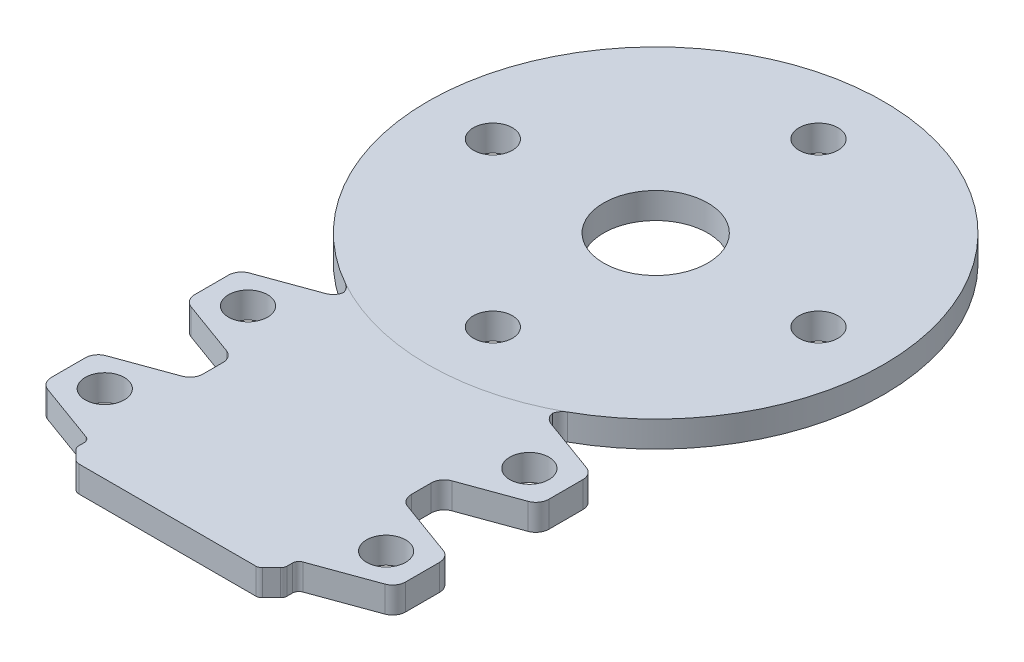
SolidWorks part; units mm, degrees
ref_plane "Front Plane" through (0, 0, 0) normal (0, 0, 1) x (1, 0, 0)
ref_plane "Top Plane" through (0, 0, 0) normal (0, 1, 0) x (1, 0, 0)
ref_plane "Right Plane" through (0, 0, 0) normal (1, 0, 0) x (0, 0, -1)
sketch "Sketch1" plane through (0, 0, 0) normal (0, 1, 0) x (1, 0, 0)
  circle A0 centre (0, 0) radius 4
  circle A1 centre (0, 0) radius 17.5
  circle A2 centre (0, 12.5) radius 1.5
  circle A3 centre (0, 0) radius 17.5
  circle A4 centre (12.5, 0) radius 1.5
  circle A5 centre (0, 0) radius 17.5
  circle A6 centre (0, -12.5) radius 1.5
  circle A7 centre (0, 0) radius 17.5
  circle A8 centre (-12.5, 0) radius 1.5
  point P18 (0, 0)
  dimension "D1" = 17.5
  dimension "D2" = 8
  dimension "D3" = 3
  dimension "D4" = 12.5
  dimension "D5" = 4
sketch "Sketch2" plane through (0, 0, 0) normal (0, 1, 0) x (1, 0, 0)
  line L0 (8, -37.5) -> (-8, -37.5)
  line L1 (-8, -4) -> (8, -4)
  line L2 (-8, -4) -> (-8, -37.5)
  line L3 (8, -4) -> (8, -37.5)
  circle A0 centre (0, 0) radius 4 construction
  circle A3 centre (0, 0) radius 17.5 construction
  arc A4 (-8, -15.5644) -> (8, -15.5644) centre (0, 0) ccw
  point P2 (0, -37.5)
  point P3 (0, -4)
  point P16 (0, -17.5)
  dimension "D1" = 16
  dimension "D2" = 20
extrude "Boss-Extrude1" add sketch "Sketch1" along normal blind 2 contours A1 A8 A6 A4 A2 A0 region at (-17.005, 0, 0)
extrude "Boss-Extrude2" add sketch "Sketch2" along normal blind 2 contours A4 L2 L0 L3 region at (0, 0, 27.177)
sketch "Sketch3" plane through (0, 0, 0) normal (0, 1, 0) x (1, 0, 0)
  line L0 (8, -37.5) -> (-8, -37.5) construction
  line L1 (-8, -15.5644) -> (-8, -37.5) construction
  line L2 (-13.6, -18.5) -> (-13.6, -22.5)
  line L3 (-13.6, -22.5) -> (-8, -24.5382)
  line L4 (-8, -24.5382) -> (-8, -16.4618)
  line L5 (-8, -16.4618) -> (-13.6, -18.5)
  line L6 (-13.6, -29.5) -> (-13.6, -33.5)
  line L7 (-13.6, -33.5) -> (-8, -35.5382)
  line L8 (-8, -35.5382) -> (-8, -27.4618)
  line L9 (-8, -27.4618) -> (-13.6, -29.5)
  circle A0 centre (-10.8, -31.5) radius 1.5
  circle A1 centre (-10.8, -20.5) radius 1.5
  point P19 (-13.6, -31.5)
  point P20 (-8, -31.5)
  point P21 (-13.6, -20.5)
  point P22 (-8, -20.5)
  dimension "D1" = 3
  dimension "D2" = 6
  dimension "D3" = 2.8
  dimension "D4" = 11
  dimension "D5" = 4
  dimension "D6" = 2.8
  dimension "D7" = 110
extrude "Boss-Extrude4" add sketch "Sketch3" along normal up to surface (2 mm away) up to face at (-12.5, 2, 1.5)
mirror "Mirror1" about plane through (0, 0, 0) normal (1, 0, 0) of "Boss-Extrude4"
fillet "Fillet1" radius 1 16 edges at (8, 1, 16.4618) (8, 1, 15.5644) (13.6, 1, 18.5) (13.6, 1, 22.5) (8, 1, 24.5382) (8, 1, 27.4618) (13.6, 1, 29.5) (13.6, 1, 33.5) (-13.6, 1, 33.5) (-13.6, 1, 29.5) (-8, 1, 27.4618) (-8, 1, 24.5382) (-13.6, 1, 22.5) (-13.6, 1, 18.5) (-8, 1, 16.4618) (-8, 1, 15.5644)
chamfer "Chamfer1" distance 1 angle 45 2 edges at (-8, 1, 37.5) (8, 1, 37.5)
fillet "Fillet2" radius 0.5 6 edges at (-7, 1, 37.5) (-8, 1, 35.5382) (7, 1, 37.5) (8, 1, 35.5382) (-8, 1, 36.5) (8, 1, 36.5)
sketch "Sketch4" plane through (0, 2, 0) normal (0, 1, 0) x (1, 0, 0)
  circle A0 centre (0, 0) radius 17.5
split line "Split Line1"
equation "\"motor_r\"= 35 / 2mm"
equation "\"boru_d\"= 16mm"
equation "\"D1@Sketch1\"=\"motor_r\""
equation "\"D1@Sketch2\"=\"boru_d\""
equation "\"D6@Sketch3\"=\"D3@Sketch3\""
